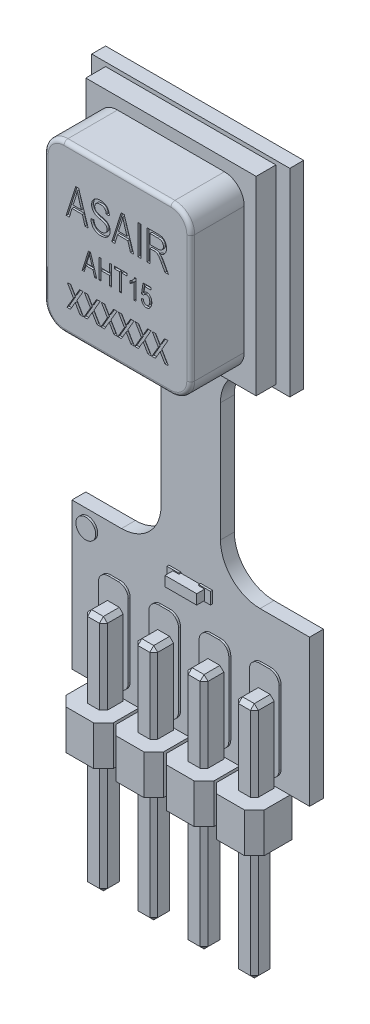
SolidWorks part; units mm, degrees
ref_plane "Alzado" through (0, 0, 0) normal (0, 0, 1) x (1, 0, 0)
ref_plane "Planta" through (0, 0, 0) normal (0, 1, 0) x (1, 0, 0)
ref_plane "Vista lateral" through (0, 0, 0) normal (1, 0, 0) x (0, 0, -1)
sketch "Sketch1" plane through (0, 0, 0) normal (0, 0, 1) x (1, 0, 0)
  line L0 (-7.0612, 0.7821) -> (18.5993, 0.7821) construction
  line L1 (-0.75, -2.5) -> (-0.75, -7.5)
  line L2 (-2.5, 2.5) -> (2.5, 2.5)
  line L3 (-2.5, 2.5) -> (-2.5, -2.5)
  line L4 (-2.5, -2.5) -> (2.5, -2.5)
  line L5 (2.5, 2.5) -> (2.5, -2.5)
  line L6 (0, -2.5) -> (0, 2.5) construction
  line L7 (-2.5, 0) -> (2.5, 0) construction
  line L8 (-0.75, -7.5) -> (-3, -7.5)
  line L9 (-3, -7.5) -> (-3, -11.2)
  line L10 (-3, -11.2) -> (3, -11.2)
  line L11 (3, -11.2) -> (3, -7.5)
  line L12 (3, -7.5) -> (0.75, -7.5)
  line L13 (0.75, -7.5) -> (0.75, -2.5)
  line L14 (-0.75, -7.5) -> (0.75, -7.5) construction
  point P2 (0, 0)
  point P13 (0, -7.5)
  dimension "D1" = 5
  dimension "D2" = 5
  dimension "D3" = 1.5
  dimension "D4" = 6
  dimension "D5" = 3.7
  dimension "D6" = 5
extrude "Boss-Extrude1" add sketch "Sketch1" against normal blind 0.35 contours L5 L2 L3 L4 | L12 L13 L4 L1 L8 L9 L10 L11 region at (0, -8.2515, 0) region at (0, 0, 0)
fillet "Fillet1" radius 1 4 edges at (0.75, -2.5, -0.175) (-0.75, -2.5, -0.175) (-0.75, -7.5, -0.175) (0.75, -7.5, -0.175)
sketch "Sketch2" plane through (0, 0, 0) normal (1, 0, 0) x (0, 0, -1)
  line L0 (-4.4118, -17.9701) -> (-4.4118, 13.5701) construction
sketch "Sketch6" plane through (0, 0, 0) normal (0, 0, 1) x (1, 0, 0)
  line L1 (-1.85, 2.1) -> (1.85, 2.1)
  line L2 (-1.85, 2.1) -> (-1.85, -2.1)
  line L3 (-1.85, -2.1) -> (1.85, -2.1)
  line L4 (1.85, 2.1) -> (1.85, -2.1)
  line L5 (0, -2.1) -> (0, 2.1) construction
  line L6 (-1.85, 0) -> (1.85, 0) construction
  point P0 (0, 0)
  dimension "D1" = 4.2
  dimension "D2" = 3.7
extrude "Boss-Extrude3" add sketch "Sketch6" along normal blind 2.2 from surface starting at face at (0, -4.8375, -0.35)
sketch "Sketch3" plane through (0, 0, 0) normal (0, 0, 1) x (1, 0, 0)
  line L1 (-2.15, 2.4) -> (2.15, 2.4)
  line L2 (-2.15, 2.4) -> (-2.15, -2.4)
  line L3 (-2.15, -2.4) -> (2.15, -2.4)
  line L4 (2.15, 2.4) -> (2.15, -2.4)
  line L5 (0, -2.4) -> (0, 2.4) construction
  line L6 (-2.15, 0) -> (2.15, 0) construction
  point P0 (0, 0)
  dimension "D1" = 4.8
  dimension "D2" = 4.3
extrude "Boss-Extrude2" add sketch "Sketch3" along normal blind 0.5
fillet "Fillet2" radius 0.5 4 edges at (1.85, 2.1, 1.175) (-1.85, 2.1, 1.175) (-1.85, -2.1, 1.175) (1.85, -2.1, 1.175)
fillet "Fillet3" radius 0.1 8 edges at (-1.7036, 1.9536, 1.85) (0, 2.1, 1.85) (1.7036, 1.9536, 1.85) (1.85, 0, 1.85) (1.7036, -1.9536, 1.85) (0, -2.1, 1.85) (-1.7036, -1.9536, 1.85) (-1.85, 0, 1.85)
sketch "Sketch7" plane through (0, 0, 0) normal (0, 0, 1) x (1, 0, 0)
  line L0 (-1.01, -9.825) -> (-1.53, -9.825) construction
  line L1 (-2.28, -8.65) -> (-1.53, -8.65)
  line L2 (-2.28, -8.65) -> (-2.28, -11)
  line L3 (-2.28, -11) -> (-1.53, -11)
  line L4 (-1.53, -8.65) -> (-1.53, -11)
  line L5 (-1.01, -8.65) -> (-0.26, -8.65)
  line L6 (-1.01, -8.65) -> (-1.01, -11)
  line L7 (-1.01, -11) -> (-0.26, -11)
  line L8 (-0.26, -8.65) -> (-0.26, -11)
  line L9 (0.26, -8.65) -> (1.01, -8.65)
  line L10 (0.26, -8.65) -> (0.26, -11)
  line L11 (0.26, -11) -> (1.01, -11)
  line L12 (1.01, -8.65) -> (1.01, -11)
  line L13 (1.53, -8.65) -> (2.28, -8.65)
  line L14 (1.53, -8.65) -> (1.53, -11)
  line L15 (1.53, -11) -> (2.28, -11)
  line L16 (2.28, -8.65) -> (2.28, -11)
  line L17 (-0.26, -9.825) -> (0.26, -9.825) construction
  line L18 (1.01, -9.825) -> (1.53, -9.825) construction
  line L19 (-3, -11.2) -> (3, -11.2) construction
  line L20 (-0.75, -7.5) -> (-3, -7.5) construction
  line L21 (-3, -7.5) -> (-3, -11.2) construction
  line L22 (-0.25, -7.85) -> (0.25, -7.85) construction
  line L23 (-0.55, -7.7) -> (-0.25, -7.7)
  line L24 (-0.55, -7.7) -> (-0.55, -8)
  line L25 (-0.55, -8) -> (-0.25, -8)
  line L26 (-0.25, -7.7) -> (-0.25, -8)
  line L27 (0.25, -7.7) -> (0.55, -7.7)
  line L28 (0.25, -7.7) -> (0.25, -8)
  line L29 (0.25, -8) -> (0.55, -8)
  line L30 (0.55, -7.7) -> (0.55, -8)
  line L31 (3, -7.5) -> (0.75, -7.5) construction
  circle A0 centre (-2.6, -7.9) radius 0.25
  point P22 (0, -9.825)
  point P42 (0, -7.85)
  dimension "D5" = 0.5
  dimension "D6" = 0.4
  dimension "D1" = 2.35
  dimension "D2" = 0.75
  dimension "D3" = 1.27
  dimension "D4" = 0.2
  dimension "D7" = 0.4
  dimension "D8" = 0.3
  dimension "D9" = 0.5
  dimension "D10" = 0.35
extrude "Boss-Extrude4" add sketch "Sketch7" along normal blind 0.05
fillet "Fillet4" radius 0.25 16 edges at (-1.53, -11, 0.025) (-2.28, -11, 0.025) (-2.28, -8.65, 0.025) (-1.53, -8.65, 0.025) (-0.26, -8.65, 0.025) (-1.01, -8.65, 0.025) (-1.01, -11, 0.025) (-0.26, -11, 0.025) (0.26, -11, 0.025) (0.26, -8.65, 0.025) (1.01, -8.65, 0.025) (1.01, -11, 0.025) (1.53, -11, 0.025) (2.28, -11, 0.025) (1.53, -8.65, 0.025) (2.28, -8.65, 0.025)
sketch "Sketch8" plane through (0, 0, 0) normal (0, 0, 1) x (1, 0, 0)
  line L1 (-0.4, -7.725) -> (0.4, -7.725)
  line L2 (-0.4, -7.725) -> (-0.4, -7.975)
  line L3 (-0.4, -7.975) -> (0.4, -7.975)
  line L4 (0.4, -7.725) -> (0.4, -7.975)
  line L6 (-0.25, -7.7) -> (-0.55, -7.7) construction
  line L7 (0.55, -7.7) -> (0.25, -7.7) construction
  line L8 (-0.55, -7.7) -> (-0.55, -8) construction
  point P9 (-0.4, -7.7)
  point P13 (0.4, -7.7)
  point P16 (-0.55, -7.85)
  point P17 (-0.4, -7.85)
  dimension "D1" = 0.25
extrude "Boss-Extrude5" add sketch "Sketch8" along normal blind 0.25
sketch "Sketch9" plane through (0, -11.2, 0) normal (0, -1, 0) x (1, 0, 0)
  line L1 (-2.505, 0.9) -> (-1.305, 0.9)
  line L2 (-2.505, 0.9) -> (-2.505, -0.3)
  line L3 (-2.505, -0.3) -> (-1.305, -0.3)
  line L4 (-1.305, 0.9) -> (-1.305, -0.3)
  line L5 (-1.905, -0.3) -> (-1.905, 0.9) construction
  line L6 (-2.505, 0.3) -> (-1.305, 0.3) construction
  line L7 (-2.03, 0.05) -> (-1.78, 0.05) construction
  line L8 (-3, 0) -> (3, 0) construction
  point P0 (-1.905, 0.3)
  point P11 (-1.905, 0.05)
  dimension "D1" = 1.2
  dimension "D2" = 0.3
extrude "Boss-Extrude6" add sketch "Sketch9" along normal blind 1
chamfer "Chamfer1" distance 0.25 angle 45 4 edges at (-1.305, -11.7, -0.3) (-2.505, -11.7, -0.3) (-1.305, -11.7, 0.9) (-2.505, -11.7, 0.9)
sketch "Sketch10" plane through (0, -12.2, 0) normal (0, -1, 0) x (1, 0, 0)
  line L0 (-1.305, -0.05) -> (-1.305, 0.65) construction
  line L1 (-2.155, 0.55) -> (-1.655, 0.55)
  line L2 (-2.155, 0.55) -> (-2.155, 0.05)
  line L3 (-2.155, 0.05) -> (-1.655, 0.05)
  line L4 (-1.655, 0.55) -> (-1.655, 0.05)
  line L5 (-1.905, 0.05) -> (-1.905, 0.55) construction
  line L6 (-2.155, 0.3) -> (-1.655, 0.3) construction
  line L7 (-1.555, 0.9) -> (-2.255, 0.9) construction
  point P0 (-1.905, 0.3)
  point P7 (-1.305, 0.3)
  point P13 (-1.905, 0.9)
  dimension "D1" = 0.5
extrude "Boss-Extrude7" add sketch "Sketch10" along normal blind 3 and the other way blind 3
chamfer "Chamfer2" distance 0.1 angle 45 13 edges at (-2.155, -9.2, 0.3) (-1.655, -9.2, 0.3) (-2.155, -10.2, 0.55) (-1.905, -9.2, 0.55) (-1.655, -10.2, 0.55) (-1.905, -15.2, 0.05) (-2.155, -13.7, 0.05) (-2.155, -15.2, 0.3) (-2.155, -13.7, 0.55) (-1.905, -15.2, 0.55) (-1.655, -13.7, 0.05) (-1.655, -15.2, 0.3) (-1.655, -13.7, 0.55)
pattern_linear "LPattern1" count 4 spacing 1.27 along (1, 0, 0) of "Boss-Extrude6", "Chamfer1", "Boss-Extrude7", "Chamfer2"
sketch "Sketch11" plane through (0, 0, 1.85) normal (0, 0, 1) x (1, 0, 0)
  line L0 (-1.5, 0.5) -> (1.5, 0.5) construction
  line L1 (-1.5, -0.5) -> (1.5, -0.5) construction
  line L2 (-1.5, -1.5) -> (1.5, -1.5) construction
  text T0 "ASAIR" font "Arial Narrow" height 0.75
  text T1 "AHT15" font "Arial Narrow" height 0.5
  text T2 "xxxxxx" font "Arial Narrow" height 0.75
  point P3 (0, -0.5)
  point P4 (0, 0.5)
  point P8 (0, -1.5)
  dimension "D1" = 0.5
  dimension "D2" = 3
  dimension "D3" = 1
  dimension "D4" = 1
extrude "Cut-Extrude1" cut sketch "Sketch11" against normal blind 0.05
